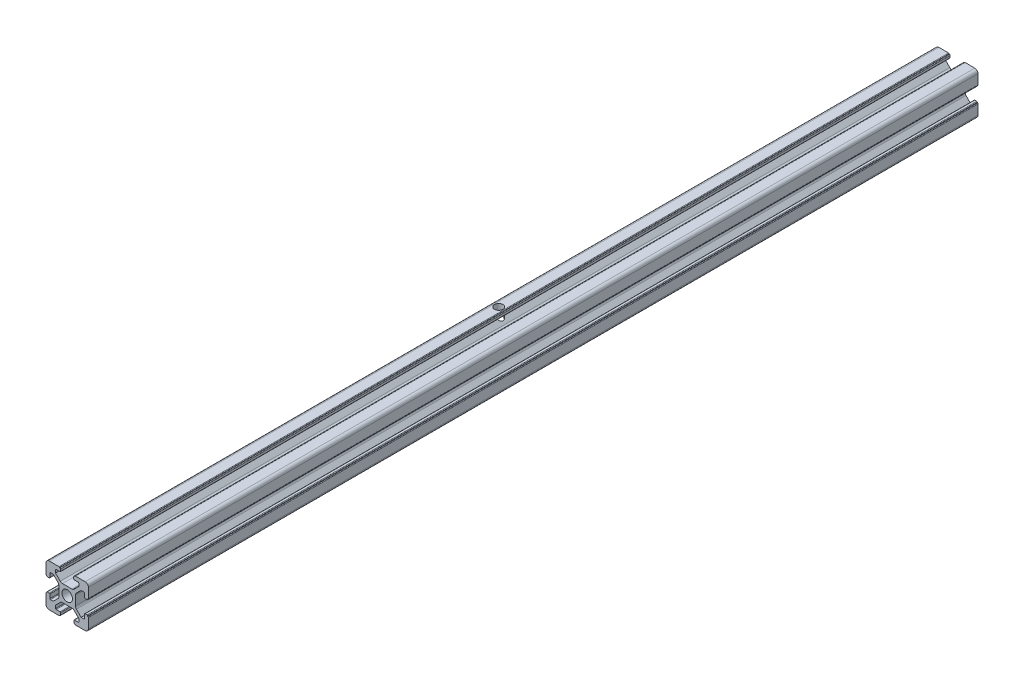
SolidWorks part; units mm, degrees
material "1060 Alloy"
ref_plane "Front Plane" through (0, 0, 0) normal (0, 0, 1) x (1, 0, 0)
ref_plane "Top Plane" through (0, 0, 0) normal (0, 1, 0) x (1, 0, 0)
ref_plane "Right Plane" through (0, 0, 0) normal (1, 0, 0) x (0, 0, -1)
sketch "Sketch1" plane through (0, 0, 0) normal (0, 0, 1) x (1, 0, 0)
  line L0 (3.8995, 3.9005) -> (10.4604, 10.4604) construction
  line L2 (-3.9002, 2.2177) -> (-3.9002, -2.2208)
  line L5 (-3.9005, 3.899) -> (3.9001, -3.8986) construction
  line L6 (-3.9, -3.901) -> (3.8995, 3.9005) construction
  line L7 (-0.0002, 10) -> (-0.0002, -9.9996) construction
  line L8 (-0.0002, -9.9996) -> (-0.0002, 10) construction
  line L9 (5.5006, 6.5619) -> (3.2793, 4.3405)
  line L14 (-10.0002, 9.9996) -> (9.9994, -10) construction
  line L15 (-9.9999, -10.0001) -> (9.9998, 10) construction
  line L16 (6.5613, 5.5012) -> (4.3401, 3.28)
  line L17 (-5.5002, 6.5603) -> (-3.279, 4.3391)
  line L18 (-6.5609, 5.4996) -> (-4.3395, 3.2783)
  line L19 (7.9206, 5.5012) -> (6.5613, 5.5012)
  line L20 (8.2006, 3.3812) -> (8.2006, 5.2212)
  line L21 (9.4206, 3.1012) -> (8.4806, 3.1012)
  line L22 (9.7006, 3.6012) -> (9.7006, 3.3812)
  line L23 (-8.5002, 9.9996) -> (-3.8802, 9.9996)
  line L24 (-3.6002, 9.7196) -> (-3.6002, 9.6996)
  line L25 (-3.6002, 9.6996) -> (-3.3802, 9.6996)
  line L26 (-3.1002, 9.4196) -> (-3.1002, 8.4796)
  line L27 (-3.3802, 8.1996) -> (-5.2202, 8.1996)
  line L28 (-5.5002, 7.9196) -> (-5.5002, 6.5603)
  line L29 (-7.9202, 5.4996) -> (-6.5609, 5.4996)
  line L30 (-8.2002, 3.3796) -> (-8.2002, 5.2196)
  line L31 (-9.4202, 3.0996) -> (-8.4802, 3.0996)
  line L32 (-9.7202, 3.5996) -> (-9.7002, 3.5996)
  line L33 (-9.7002, 3.5996) -> (-9.7002, 3.3796)
  line L34 (-10.0002, 8.4996) -> (-10.0002, 3.8796)
  line L35 (10.0006, 8.5012) -> (10.0006, 3.8812)
  line L36 (8.5006, 10.0012) -> (3.8806, 10.0012)
  line L37 (3.6006, 9.7012) -> (3.3806, 9.7012)
  line L38 (3.1006, 9.4212) -> (3.1006, 8.4812)
  line L39 (3.3806, 8.2012) -> (5.2206, 8.2012)
  line L40 (5.5006, 7.9212) -> (5.5006, 6.5619)
  line L41 (6.5629, -5.4996) -> (4.3415, -3.2783)
  line L42 (5.5022, -6.5603) -> (3.281, -4.3391)
  line L43 (5.5022, -7.9196) -> (5.5022, -6.5603)
  line L44 (3.3822, -8.1996) -> (5.2222, -8.1996)
  line L45 (3.1022, -9.4196) -> (3.1022, -8.4796)
  line L46 (3.6022, -9.6996) -> (3.3822, -9.6996)
  line L47 (8.5022, -9.9996) -> (3.8822, -9.9996)
  line L48 (10.0022, -8.4996) -> (10.0022, -3.8796)
  line L49 (9.7022, -3.5996) -> (9.7022, -3.3796)
  line L50 (9.4222, -3.0996) -> (8.4822, -3.0996)
  line L51 (8.2022, -3.3796) -> (8.2022, -5.2196)
  line L52 (7.9222, -5.4996) -> (6.5629, -5.4996)
  line L53 (-5.4986, -6.5619) -> (-3.2773, -4.3405)
  line L54 (-6.5593, -5.5012) -> (-4.3395, -3.2814)
  line L55 (-7.9186, -5.5012) -> (-6.5593, -5.5012)
  line L56 (-8.1986, -3.3812) -> (-8.1986, -5.2212)
  line L57 (-9.4186, -3.1012) -> (-8.4786, -3.1012)
  line L58 (-9.6986, -3.6012) -> (-9.6986, -3.3812)
  line L59 (-9.9986, -8.5012) -> (-9.9986, -3.8812)
  line L60 (-8.4986, -10.0012) -> (-3.8786, -10.0012)
  line L61 (-3.5986, -9.7012) -> (-3.3786, -9.7012)
  line L62 (-3.0986, -9.4212) -> (-3.0986, -8.4812)
  line L63 (-3.3786, -8.2012) -> (-5.2186, -8.2012)
  line L64 (-5.4986, -7.9212) -> (-5.4986, -6.5619)
  line L65 (-2.233, 3.8998) -> (2.2187, 3.9012)
  line L66 (3.9008, 2.234) -> (3.9022, -2.2177)
  line L67 (2.235, -3.8998) -> (-2.2167, -3.9012)
  line L68 (3.6006, 9.7212) -> (3.6006, 9.6996)
  line L69 (9.7006, 3.6012) -> (9.7206, 3.6012)
  line L70 (-9.6986, -3.6012) -> (-9.7186, -3.6012)
  line L71 (-3.5986, -9.7012) -> (-3.5986, -9.7212)
  line L72 (3.6022, -9.6996) -> (3.6022, -9.7196)
  line L73 (9.7222, -3.5996) -> (9.7022, -3.5996)
  arc A0 (-3.6002, 9.7196) -> (-3.8802, 9.9996) centre (-3.8802, 9.7196) ccw
  arc A1 (-3.3802, 9.6996) -> (-3.1002, 9.4196) centre (-3.3802, 9.4196) cw
  arc A2 (-3.1002, 8.4796) -> (-3.3802, 8.1996) centre (-3.3802, 8.4796) cw
  arc A3 (-10.0002, 8.4996) -> (-8.5002, 9.9996) centre (-8.5002, 8.4996) cw
  arc A4 (-8.2002, 3.3796) -> (-8.4802, 3.0996) centre (-8.4802, 3.3796) cw
  arc A5 (-9.4202, 3.0996) -> (-9.7002, 3.3796) centre (-9.4202, 3.3796) cw
  arc A6 (-9.7202, 3.5996) -> (-10.0002, 3.8796) centre (-9.7202, 3.8796) cw
  arc A7 (-3.279, 4.3391) -> (-2.233, 3.8998) centre (-2.2183, 5.3997) ccw
  arc A8 (-4.3395, 3.2783) -> (-3.9002, 2.2177) centre (-5.4002, 2.2177) cw
  arc A9 (-7.9202, 5.4996) -> (-8.2002, 5.2196) centre (-7.9202, 5.2196) ccw
  arc A10 (-5.2202, 8.1996) -> (-5.5002, 7.9196) centre (-5.2202, 7.9196) ccw
  arc A12 (-4.3395, -3.2814) -> (-3.9002, -2.2208) centre (-5.4002, -2.2208) ccw
  arc A13 (8.2006, 5.2212) -> (7.9206, 5.5012) centre (7.9206, 5.2212) ccw
  arc A14 (8.4806, 3.1012) -> (8.2006, 3.3812) centre (8.4806, 3.3812) cw
  arc A15 (9.7006, 3.3812) -> (9.4206, 3.1012) centre (9.4206, 3.3812) cw
  arc A16 (9.7206, 3.6012) -> (10.0006, 3.8812) centre (9.7206, 3.8812) ccw
  arc A17 (8.5006, 10.0012) -> (10.0006, 8.5012) centre (8.5006, 8.5012) cw
  arc A18 (3.6006, 9.7212) -> (3.8806, 10.0012) centre (3.8806, 9.7212) cw
  arc A19 (3.1006, 9.4212) -> (3.3806, 9.7012) centre (3.3806, 9.4212) cw
  arc A20 (3.3806, 8.2012) -> (3.1006, 8.4812) centre (3.3806, 8.4812) cw
  arc A21 (5.5006, 7.9212) -> (5.2206, 8.2012) centre (5.2206, 7.9212) ccw
  arc A22 (3.2793, 4.3405) -> (2.2187, 3.9012) centre (2.2187, 5.4012) cw
  arc A23 (4.3401, 3.28) -> (3.9008, 2.234) centre (5.4007, 2.2193) ccw
  arc A25 (5.2222, -8.1996) -> (5.5022, -7.9196) centre (5.2222, -7.9196) ccw
  arc A26 (3.1022, -8.4796) -> (3.3822, -8.1996) centre (3.3822, -8.4796) cw
  arc A27 (3.3822, -9.6996) -> (3.1022, -9.4196) centre (3.3822, -9.4196) cw
  arc A28 (3.6022, -9.7196) -> (3.8822, -9.9996) centre (3.8822, -9.7196) ccw
  arc A29 (10.0022, -8.4996) -> (8.5022, -9.9996) centre (8.5022, -8.4996) cw
  arc A30 (9.7222, -3.5996) -> (10.0022, -3.8796) centre (9.7222, -3.8796) cw
  arc A31 (9.4222, -3.0996) -> (9.7022, -3.3796) centre (9.4222, -3.3796) cw
  arc A32 (8.2022, -3.3796) -> (8.4822, -3.0996) centre (8.4822, -3.3796) cw
  arc A33 (7.9222, -5.4996) -> (8.2022, -5.2196) centre (7.9222, -5.2196) ccw
  arc A34 (4.3415, -3.2783) -> (3.9022, -2.2177) centre (5.4022, -2.2177) cw
  arc A35 (3.281, -4.3391) -> (2.235, -3.8998) centre (2.2203, -5.3997) ccw
  circle A36 centre (0.001, -0.001) radius 2.5 construction
  arc A37 (-8.1986, -5.2212) -> (-7.9186, -5.5012) centre (-7.9186, -5.2212) ccw
  arc A38 (-8.4786, -3.1012) -> (-8.1986, -3.3812) centre (-8.4786, -3.3812) cw
  arc A39 (-9.6986, -3.3812) -> (-9.4186, -3.1012) centre (-9.4186, -3.3812) cw
  arc A40 (-9.7186, -3.6012) -> (-9.9986, -3.8812) centre (-9.7186, -3.8812) ccw
  arc A41 (-8.4986, -10.0012) -> (-9.9986, -8.5012) centre (-8.4986, -8.5012) cw
  arc A42 (-3.5986, -9.7212) -> (-3.8786, -10.0012) centre (-3.8786, -9.7212) cw
  arc A43 (-3.0986, -9.4212) -> (-3.3786, -9.7012) centre (-3.3786, -9.4212) cw
  arc A44 (-3.3786, -8.2012) -> (-3.0986, -8.4812) centre (-3.3786, -8.4812) cw
  arc A45 (-5.4986, -7.9212) -> (-5.2186, -8.2012) centre (-5.2186, -7.9212) ccw
  arc A46 (-3.2773, -4.3405) -> (-2.2167, -3.9012) centre (-2.2167, -5.4012) cw
  arc A48 (-4.3381, -3.28) -> (-3.8988, -2.234) centre (-5.3987, -2.2193) ccw [skipped]
  point P0 (0, 0)
  point P9 (-0.0002, 0.0002)
  point P12 (-0.0003, -0.0003)
  point P43 (-3.6002, 9.9996)
  point P46 (-3.1002, 9.6996)
  point P49 (-3.1002, 8.1996)
  point P55 (-8.2002, 3.0996)
  point P58 (-9.7002, 3.0996)
  point P61 (-10.0002, 3.5996)
  point P64 (-2.8395, 3.8996)
  point P67 (-3.9002, 2.839)
  point P70 (-8.2002, 5.4996)
  point P73 (-5.5002, 8.1996)
  point P184 (0.001, 0)
  dimension "D14" = 0.28
  dimension "D15" = 0.28
  dimension "D16" = 0.28
  dimension "D17" = 1.5
  dimension "D18" = 0.28
  dimension "D19" = 1.5
  dimension "D20" = 1.5
  dimension "D21" = 0.28
  dimension "D23" = 5
  dimension "D27" = 1.5
  dimension "D1" = 7.8
  dimension "D2" = 7.8
  dimension "D3" = 3.1
  dimension "D4" = 3.6
  dimension "D5" = 20
  dimension "D6" = 20
  dimension "D7" = 0.75
  dimension "D8" = 1.8
  dimension "D9" = 5.5
  dimension "D10" = 6.4
  dimension "D11" = 6.4
  dimension "D12" = 3.7627
  dimension "D13" = 0.3
  dimension "D24" = 4.62
  dimension "D25" = 3.9005
  dimension "D26" = 7.801
  dimension "D22" = 4
extrude "Boss-Extrude1" add sketch "Sketch1" along normal blind 420 contours L53 A46 L67 A35 L42 L43 A25 L44 A26 L45 A27 L46 L72 A28 L47 A29 L48 A30 L73 L49 A31 L50 A32 L51 A33 L52 L41 A34 L66 A23 L16 L19 A13 L20 A14 L21 A15 L22 L69 A16 L35 A17 L36 A18 L68 L37 A19 L38 A20 region at (0.0009, 0, 0)
sketch3d "3DSketch2"
  circle A0 centre (0, 0, 0) radius 2.5
  point P2 (0, 0, 2.5)
extrude "Cut-Extrude1" cut sketch "3DSketch2" along direction (0, 0, 1) on the side of the normal through all contours A0
sketch "Sketch2" plane through (0, 9.9996, 0) normal (0, 1, 0) x (1, 0, 0)
  circle A0 centre (-6.25, -210) radius 2
extrude "Cut-Extrude2" cut sketch "Sketch2" against normal through all
